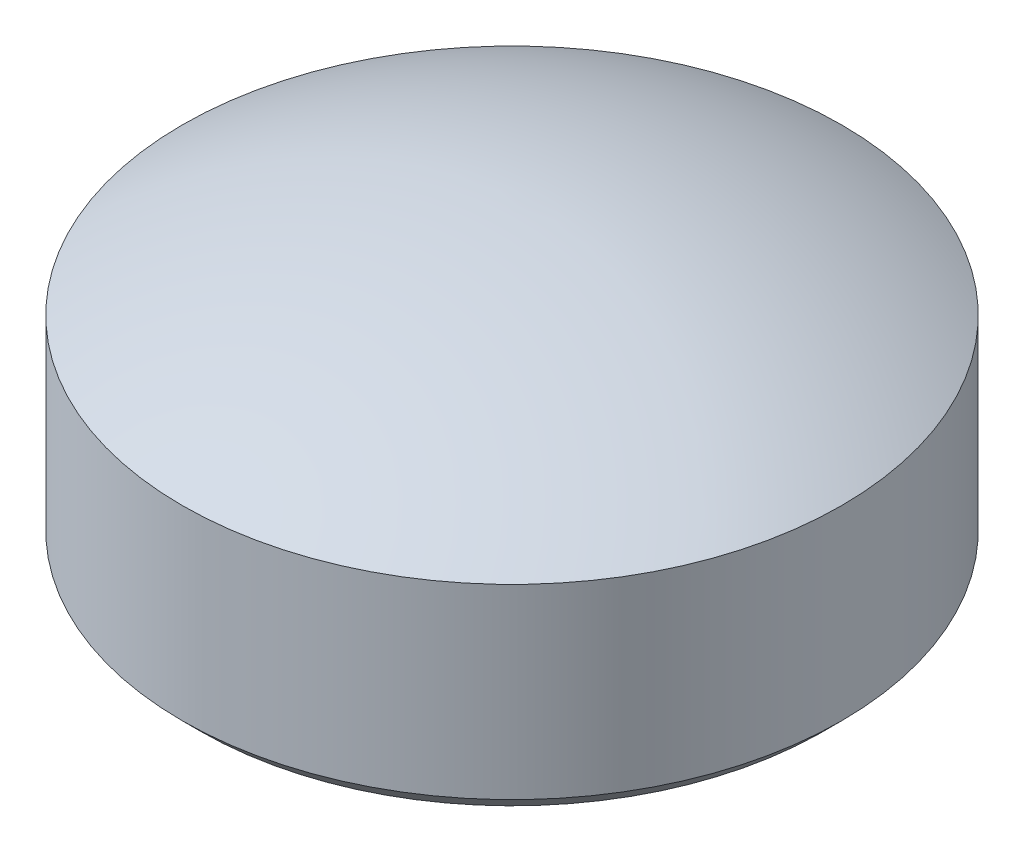
SolidWorks part; units mm, degrees
material "1.0060 (E335)"
ref_plane "Front Plane" through (0, 0, 0) normal (0, 0, 1) x (1, 0, 0)
ref_plane "Top Plane" through (0, 0, 0) normal (0, 1, 0) x (1, 0, 0)
ref_plane "Right Plane" through (0, 0, 0) normal (1, 0, 0) x (0, 0, -1)
sketch "Sketch1" plane through (0, 0, 0) normal (0, 0, 1) x (1, 0, 0)
  line L0 (0, 8) -> (0, -10)
  line L1 (0, -10) -> (-18, -10)
  arc A0 (0, 8) -> (-18, -10) centre (0, -10) ccw
  dimension "D1" = 18
  dimension "D2" = 8
revolve "Revolve1" add sketch "Sketch1" angle 360 about L0
sketch "Sketch2" plane through (0, 0, 0) normal (0, 1, 0) x (1, 0, 0)
  circle A0 centre (0, 0) radius 18
  circle A1 centre (0, 0) radius 18 construction
  circle A2 centre (0, 0) radius 9
  dimension "D1" = 18
extrude "Cut-Extrude1" cut sketch "Sketch2" along normal through all both and the other way through all
extrude "Cut-Extrude2" cut sketch "Sketch2<5>" against normal through all contours A2
sketch "Sketch2<5>" plane through (0, 0, 0) normal (0, 1, 0) x (1, 0, 0) same geometry as "Sketch2"
chamfer "Chamfer1" distance 0.5 angle 45 1 edges at (0, 0, 9)
